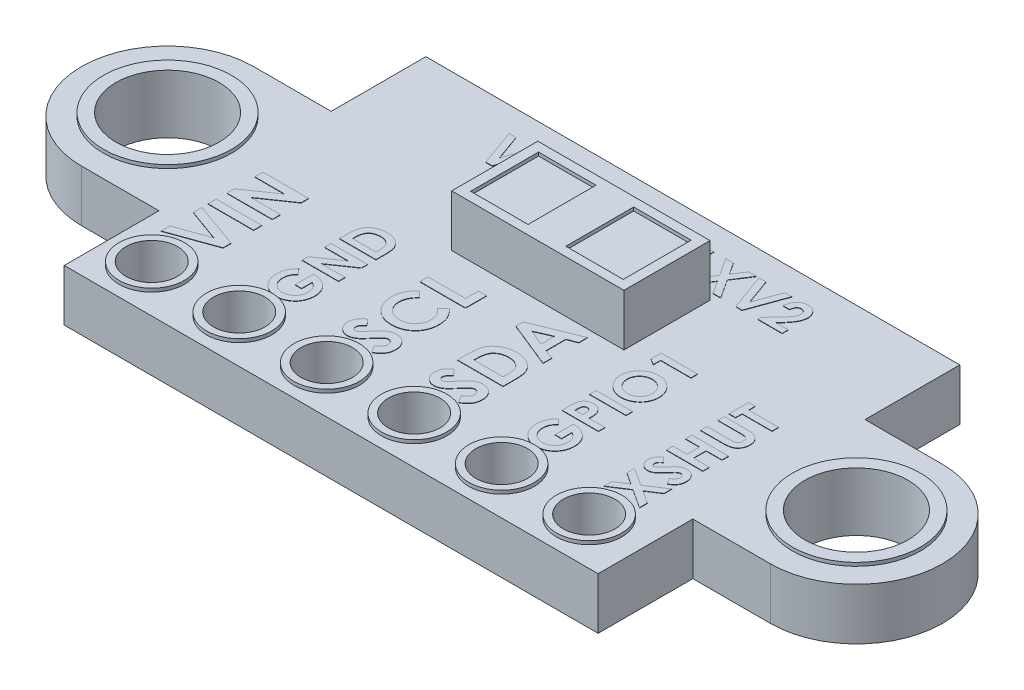
SolidWorks part; units mm, degrees
ref_plane "Ön Düzlem" through (0, 0, 0) normal (0, 0, 1) x (1, 0, 0)
ref_plane "Üst Düzlem" through (0, 0, 0) normal (0, 1, 0) x (1, 0, 0)
ref_plane "Sağ Düzlem" through (0, 0, 0) normal (1, 0, 0) x (0, 0, -1)
sketch "Çizim1" plane through (0, 0, 0) normal (0, 1, 0) x (1, 0, 0)
  line L0 (-10, 0) -> (10, 0) construction
  line L1 (-7.75, -5.25) -> (7.75, -5.25)
  line L2 (-7.75, -5.25) -> (-7.75, -2.5)
  line L3 (-7.75, 5.25) -> (7.75, 5.25)
  line L4 (7.75, -5.25) -> (7.75, -2.5)
  line L5 (-7.75, -5.25) -> (7.75, 5.25) construction
  line L6 (-7.75, 5.25) -> (7.75, -5.25) construction
  line L7 (-10, 2.5) -> (-7.75, 2.5)
  line L8 (-10, -2.5) -> (-7.75, -2.5)
  line L9 (10, -2.5) -> (7.75, -2.5)
  line L10 (10, 2.5) -> (7.75, 2.5)
  line L11 (-7.75, 2.5) -> (-7.75, 5.25)
  line L12 (7.75, 2.5) -> (7.75, 5.25)
  circle A0 centre (-10, 0) radius 1.5
  circle A1 centre (10, 0) radius 1.5
  arc A3 (-10, 2.5) -> (-10, -2.5) centre (-10, 0) ccw
  arc A4 (10, -2.5) -> (10, 2.5) centre (10, 0) ccw
  circle A5 centre (-10, 0) radius 2.5 construction
  circle A6 centre (10, 0) radius 2.5 construction
  point P0 (0, 0)
  dimension "D3" = 3
  dimension "D5" = 20
  dimension "D4" = 5
  dimension "D1" = 15.5
  dimension "D2" = 10.5
extrude "Yükseklik-Ekstrüzyon1" add sketch "Çizim1" along normal blind 1.5
sketch "Çizim2" plane through (0, 1.5, 0) normal (0, 1, 0) x (1, 0, 0)
  line L0 (0, 5.25) -> (0, 2) construction
  line L1 (7.75, 5.25) -> (-7.75, 5.25) construction
  line L3 (-2.5, 0.75) -> (2.5, 0.75)
  line L4 (-2.5, 0.75) -> (-2.5, 3.25)
  line L5 (-2.5, 3.25) -> (2.5, 3.25)
  line L6 (2.5, 0.75) -> (2.5, 3.25)
  line L7 (-2.5, 0.75) -> (2.5, 3.25) construction
  line L8 (-2.5, 3.25) -> (2.5, 0.75) construction
  dimension "D1" = 5
  dimension "D2" = 2.5
  dimension "D3" = 3.25
extrude "Yükseklik-Ekstrüzyon2" add sketch "Çizim2" along normal blind 1.5
sketch "Çizim3" plane through (0, 3, 0) normal (0, 1, 0) x (1, 0, 0)
  line L3 (0, 3.25) -> (0, 0.75) construction
  line L7 (2.5, 3.25) -> (-2.5, 3.25) construction
  line L12 (-2.5, 0.75) -> (2.5, 0.75) construction
  line L13 (0, 2) -> (-2.5, 2) construction
  line L14 (-2.5, 3.25) -> (-2.5, 0.75) construction
  line L15 (2.2157, 1.014) -> (0.548, 2.986) construction
  line L16 (-2.2157, 2.986) -> (-0.548, 2.986)
  line L17 (-2.2157, 2.986) -> (-2.2157, 1.014)
  line L18 (-2.2157, 1.014) -> (-0.548, 1.014)
  line L19 (-0.548, 2.986) -> (-0.548, 1.014)
  line L20 (-2.2157, 2.986) -> (-0.548, 1.014) construction
  line L21 (-2.2157, 1.014) -> (-0.548, 2.986) construction
  line L22 (2.2157, 2.986) -> (0.548, 1.014) construction
  line L23 (0.548, 2.986) -> (0.548, 1.014)
  line L24 (2.2157, 1.014) -> (0.548, 1.014)
  line L25 (2.2157, 2.986) -> (2.2157, 1.014)
  line L26 (2.2157, 2.986) -> (0.548, 2.986)
  point P10 (-1.3818, 2)
  point P19 (1.3818, 2)
extrude "Kes-Ekstrüzyon1" cut sketch "Çizim3" against normal blind 0.1
sketch "Çizim4" plane through (0, 1.5, 0) normal (0, 1, 0) x (1, 0, 0)
  line L0 (0, 0) -> (0, -1.1087) construction
  circle A0 centre (10, 0) radius 1.8604
  circle A1 centre (10, 0) radius 1.5 construction
  circle A2 centre (10, 0) radius 1.5
  circle A3 centre (-10, 0) radius 1.5
  circle A4 centre (-10, 0) radius 1.8604
extrude "Yükseklik-Ekstrüzyon3" add sketch "Çizim4" along normal blind 0.1 and the other way blind 1.6
sketch "Çizim5" plane through (0, 1.5, 0) normal (0, 1, 0) x (1, 0, 0)
  line L0 (-7.75, -5.25) -> (-7.75, -3.98) construction
  line L1 (-7.75, -2.5) -> (-7.75, -5.25) construction
  line L2 (-7.75, -3.98) -> (-6.48, -3.98) construction
  circle A0 centre (-6.48, -3.98) radius 0.75
  circle A1 centre (-3.94, -3.98) radius 0.75
  circle A2 centre (-1.4, -3.98) radius 0.75
  circle A3 centre (1.14, -3.98) radius 0.75
  circle A4 centre (3.68, -3.98) radius 0.75
  circle A5 centre (6.22, -3.98) radius 0.75
  dimension "D1" = 6
extrude "Kes-Ekstrüzyon2" cut sketch "Çizim5" against normal blind 3.1
sketch "Çizim6" plane through (0, 1.5, 0) normal (0, 1, 0) x (1, 0, 0)
  circle A0 centre (-6.48, -3.98) radius 0.75 construction
  circle A1 centre (-6.48, -3.98) radius 0.75
  circle A2 centre (-6.48, -3.98) radius 0.95
  dimension "D1" = 0.2
extrude "Yükseklik-Ekstrüzyon4" add sketch "Çizim6" along normal blind 0.1 and the other way blind 1.6
pattern_linear "LÇoğaltma1" count 6 spacing 2.54 along (1, 0, 0) of "Yükseklik-Ekstrüzyon4"
sketch "Çizim7" plane through (0, 1.5, 0) normal (0, 1, 0) x (1, 0, 0)
  line L0 (-3.3625, -3.03) -> (-3.3625, 1.2923) construction
  line L1 (-5.8779, -3.03) -> (-5.8779, 1.2923) construction
  line L2 (-0.8471, -3.03) -> (-0.8471, 1.2923) construction
  line L3 (1.6682, -3.03) -> (1.6682, 1.2923) construction
  line L4 (4.1836, -3.03) -> (4.1836, 1.2923) construction
  line L5 (6.6989, -3.03) -> (6.6989, 1.2923) construction
  text T0 "VIN" font "Century Gothic" height in points 5
  text T1 "GND" font "Century Gothic" height in points 4
  text T2 "<b>SCL</b>" font "Century Gothic" height in points 5
  text T3 "SDA" font "Century Gothic" height in points 5
  text T4 "GPIO1" font "Century Gothic" height in points 4
  text T5 "<b>XSHUT</b>" font "Century Gothic" height in points 4
  dimension "D1" = 6
extrude "Yükseklik-Ekstrüzyon5" add sketch "Çizim7" along normal blind 0.01
sketch "Çizim8" plane through (0, 1.5, 0) normal (0, 1, 0) x (1, 0, 0)
  line L0 (-5.0829, 3.4564) -> (4.9171, 3.4564) construction
  line L1 (0, 0) -> (0, 5.25) construction
  line L2 (7.75, 5.25) -> (-7.75, 5.25) construction
  text T0 "VL53L0/1XV2" font "Century Gothic" height in points 4
extrude "Yükseklik-Ekstrüzyon6" add sketch "Çizim8" along normal blind 0.01
sketch "Çizim9" plane through (0, 0, 0) normal (0, -1, 0) x (1, 0, 0)
  line L0 (-1.7136, -3.2806) -> (-1.2276, -3.2806)
  line L1 (2.6326, 0.7695) -> (3.9286, 0.7695)
  line L2 (2.6326, 0.7695) -> (2.6326, -2.0656)
  line L3 (2.6326, -2.0656) -> (3.9286, -2.0656)
  line L4 (3.9286, 0.7695) -> (3.9286, -2.0656)
  line L5 (2.6326, 0.7695) -> (3.9286, -2.0656) construction
  line L6 (2.6326, -2.0656) -> (3.9286, 0.7695) construction
  line L7 (-2.7136, -3.2806) -> (-2.2276, -3.2806)
  line L8 (-2.7136, -3.2806) -> (-2.7136, -4.3336)
  line L9 (-2.7136, -4.3336) -> (-2.2276, -4.3336)
  line L10 (-2.2276, -3.2806) -> (-2.2276, -4.3336)
  line L11 (-2.7136, -3.2806) -> (-2.2276, -4.3336) construction
  line L12 (-2.7136, -4.3336) -> (-2.2276, -3.2806) construction
  line L17 (-1.7136, -3.2806) -> (-1.7136, -4.3336)
  line L18 (-1.7136, -4.3336) -> (-1.2276, -4.3336)
  line L23 (-1.2276, -3.2806) -> (-1.2276, -4.3336)
  line L24 (-1.7136, -3.2806) -> (-1.2276, -4.3336) construction
  line L25 (-1.7136, -4.3336) -> (-1.2276, -3.2806) construction
  line L26 (-0.7136, -3.2806) -> (-0.2276, -3.2806)
  line L27 (-0.7136, -3.2806) -> (-0.7136, -4.3336)
  line L28 (-0.7136, -4.3336) -> (-0.2276, -4.3336)
  line L29 (-0.2276, -3.2806) -> (-0.2276, -4.3336)
  line L30 (-0.7136, -3.2806) -> (-0.2276, -4.3336) construction
  line L31 (-0.7136, -4.3336) -> (-0.2276, -3.2806) construction
  line L32 (-5.7336, 1.0241) -> (-5.2741, 1.0241)
  line L33 (-6.7336, 1.0241) -> (-6.2741, 1.0241)
  line L34 (-6.7336, 1.0241) -> (-6.7336, -0.1705)
  line L35 (-6.7336, -0.1705) -> (-6.2741, -0.1705)
  line L36 (-6.2741, 1.0241) -> (-6.2741, -0.1705)
  line L37 (-6.7336, 1.0241) -> (-6.2741, -0.1705) construction
  line L38 (-6.7336, -0.1705) -> (-6.2741, 1.0241) construction
  line L39 (-5.7336, 1.0241) -> (-5.7336, -0.1705)
  line L40 (-5.7336, -0.1705) -> (-5.2741, -0.1705)
  line L41 (-5.2741, 1.0241) -> (-5.2741, -0.1705)
  line L42 (-5.7336, 1.0241) -> (-5.2741, -0.1705) construction
  line L43 (-5.7336, -0.1705) -> (-5.2741, 1.0241) construction
  point P0 (3.2806, -0.648)
  point P5 (-2.4706, -3.8071)
  point P10 (-6.5038, 0.4268)
  point P11 (-1.4706, -3.8071)
  point P16 (-0.4706, -3.8071)
  point P27 (-5.5038, 0.4268)
  dimension "D1" = 3
  dimension "D2" = 2
extrude "Yükseklik-Ekstrüzyon7" add sketch "Çizim9" along normal blind 1
sketch "Çizim10" plane through (0, -1, 0) normal (0, -1, 0) x (1, 0, 0)
  line L0 (-0.2276, -4.3336) -> (-0.2276, -3.2806) construction
  line L1 (-0.2276, -3.2806) -> (-0.7136, -3.2806) construction
  line L2 (-0.7136, -3.2806) -> (-0.7136, -4.3336) construction
  line L3 (-0.7136, -4.3336) -> (-0.2276, -4.3336) construction
  line L4 (-5.2741, -0.1705) -> (-5.2741, 1.0241)
  line L5 (-5.2741, 1.0241) -> (-5.7336, 1.0241)
  line L6 (-5.7336, 1.0241) -> (-5.7336, -0.1705)
  line L7 (-5.7336, -0.1705) -> (-5.2741, -0.1705)
  line L8 (-5.2741, -0.1705) -> (-5.2741, 1.0241)
  line L9 (-5.2741, 1.0241) -> (-5.7336, 1.0241)
  line L10 (-5.7336, 1.0241) -> (-5.7336, -0.1705)
  line L11 (-5.7336, -0.1705) -> (-5.2741, -0.1705)
  line L12 (-6.2741, -0.1705) -> (-6.2741, 1.0241)
  line L13 (-6.2741, 1.0241) -> (-6.7336, 1.0241)
  line L14 (-6.7336, 1.0241) -> (-6.7336, -0.1705)
  line L15 (-6.7336, -0.1705) -> (-6.2741, -0.1705)
  line L16 (-6.2741, -0.1705) -> (-6.2741, 1.0241)
  line L17 (-6.2741, 1.0241) -> (-6.7336, 1.0241)
  line L18 (-6.7336, 1.0241) -> (-6.7336, -0.1705)
  line L19 (-6.7336, -0.1705) -> (-6.2741, -0.1705)
  line L20 (-1.2276, -4.3336) -> (-1.2276, -3.2806) construction
  line L21 (-1.2276, -3.2806) -> (-1.7136, -3.2806) construction
  line L22 (-1.7136, -3.2806) -> (-1.7136, -4.3336) construction
  line L23 (-1.7136, -4.3336) -> (-1.2276, -4.3336) construction
  line L24 (-2.2276, -4.3336) -> (-2.2276, -3.2806) construction
  line L25 (-2.2276, -3.2806) -> (-2.7136, -3.2806) construction
  line L26 (-2.7136, -3.2806) -> (-2.7136, -4.3336) construction
  line L27 (-2.7136, -4.3336) -> (-2.2276, -4.3336) construction
  line L28 (-0.2276, -4.3336) -> (-0.2276, -3.2806)
  line L29 (-0.2276, -3.2806) -> (-0.7136, -3.2806)
  line L30 (-0.7136, -3.2806) -> (-0.7136, -4.3336)
  line L31 (-0.7136, -4.3336) -> (-0.2276, -4.3336)
  line L32 (-1.2276, -4.3336) -> (-1.2276, -3.2806)
  line L33 (-1.2276, -3.2806) -> (-1.7136, -3.2806)
  line L34 (-1.7136, -3.2806) -> (-1.7136, -4.3336)
  line L35 (-1.7136, -4.3336) -> (-1.2276, -4.3336)
  line L36 (-2.2276, -4.3336) -> (-2.2276, -3.2806)
  line L37 (-2.2276, -3.2806) -> (-2.7136, -3.2806)
  line L38 (-2.7136, -3.2806) -> (-2.7136, -4.3336)
  line L39 (-2.7136, -4.3336) -> (-2.2276, -4.3336)
  dimension "D1" = 0
  dimension "D2" = 0
extrude "Kes-Ekstrüzyon3" cut sketch "Çizim10" against normal blind 0.5
